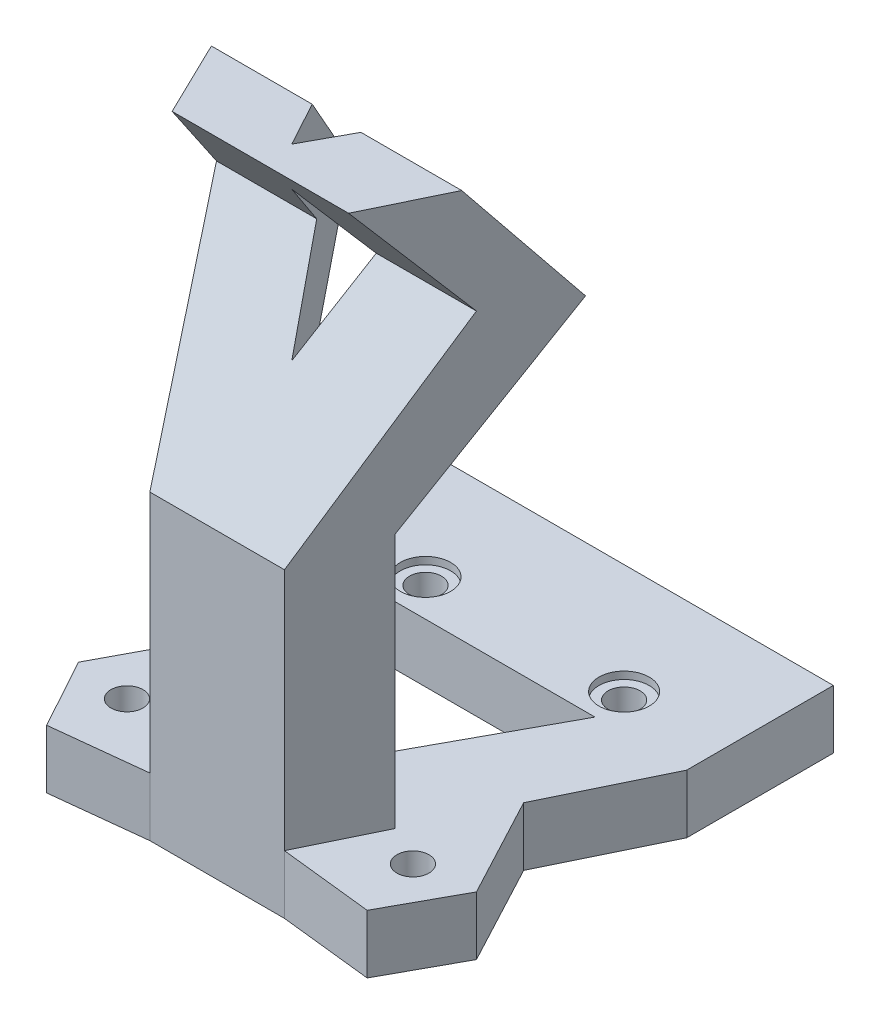
SolidWorks part; units mm, degrees
ref_plane "Front Plane" through (0, 0, 0) normal (0, 0, 1) x (1, 0, 0)
ref_plane "Top Plane" through (0, 0, 0) normal (0, 1, 0) x (1, 0, 0)
ref_plane "Right Plane" through (0, 0, 0) normal (1, 0, 0) x (0, 0, -1)
sketch "Sketch2" plane through (0, 0, 0) normal (0, 1, 0) x (1, 0, 0)
  line L0 (-47.1248, 0) -> (47.1248, 0) construction
  line L1 (-131.7903, 0) -> (131.7903, 0) construction
  line L2 (47.1248, 0) -> (-58.69, 0) construction
  line L3 (0, 0) -> (0, 70.6117) construction
  line L4 (0, 70.6117) -> (0, -77.9144) construction
  line L5 (-27.1, 0) -> (27.1, 0) construction
  line L6 (27.1, 0) -> (27.1, 20) construction
  line L7 (-27.1, 0) -> (27.1, 0)
  line L8 (27.1, 0) -> (27.1, 20)
  line L9 (27.1, 20) -> (-27.1, 20)
  line L10 (0, -131.4832) -> (0, 131.4832) construction
  line L11 (-27.1, 0) -> (-27.1, 20) construction
  line L12 (-47.1248, 0) -> (58.69, 0) construction
  line L13 (-27.1, 0) -> (-27.1, 20)
  point P4 (0, 0)
  point P8 (0, 0)
  point P19 (0, 20)
  dimension "D1" = 20
  dimension "D2" = 27.1
extrude "Boss-Extrude1" add sketch "Sketch2" along normal blind 8
ref_plane "Plane1" through (0, 5, 0) normal (0, 1, 0) x (1, 0, 0)
sketch "Sketch4" plane through (0, 8, 0) normal (0, 1, 0) x (1, 0, 0)
  line L0 (-27.1, 10) -> (-27.1, 0) construction
  line L1 (-4.4, 0) -> (4.4, 0) construction
  line L2 (-27.1, 20) -> (-27.1, 0) construction
  line L3 (-27.1, 0) -> (-27.1, 10) construction
  line L4 (-27.1, 10) -> (27.1, 10) construction
  line L5 (27.1, 0) -> (27.1, 20) construction
  line L6 (27.1, 10) -> (27.1, 0) construction
  line L8 (27.1, 0) -> (27.1, 5) construction
  line L9 (27.1, 5) -> (-27.1, 5) construction
  line L10 (0, 0) -> (27.1, 0) construction
  line L11 (-27.1, 0) -> (27.1, 0) construction
  line L12 (27.1, 0) -> (13.55, 0) construction
  line L13 (-13.55, 10) -> (-13.55, 0) construction
  line L14 (13.55, 0) -> (13.55, 10) construction
  line L15 (0, -4.4) -> (0, 4.4) construction
  circle A0 centre (13.55, 5) radius 2.1825
  circle A1 centre (-13.55, 5) radius 2.1825
  dimension "D1" = 4.365
extrude "Cut-Extrude1" cut sketch "Sketch4" against normal blind 10
sketch "Sketch5" plane through (0, 5, 0) normal (0, 1, 0) x (1, 0, 0)
  line L2 (-4.4, 0) -> (4.4, 0) construction
  line L4 (-27.1, 0) -> (-9.1823, -36.9742)
  line L6 (0, -24.7427) -> (0, 24.7427) construction
  line L7 (-9.1823, -36.9742) -> (9.1823, -36.9742)
  line L9 (27.1, 0) -> (9.1823, -36.9742)
  line L12 (-27.1, 0) -> (-14.58, 0)
  line L16 (-14.58, 0) -> (0, -26.7931)
  line L17 (14.58, 0) -> (0, -26.7931)
  line L18 (27.1, 0) -> (14.58, 0)
  line L19 (-27.1, 20) -> (-27.1, 0) construction
  point P17 (0, -36.9742)
  point P18 (0, 0)
  dimension "D3" = 18.3647
extrude "Boss-Extrude2" add sketch "Sketch5" along normal blind 3
sketch "Sketch9" plane through (0, 8, 0) normal (0, 1, 0) x (1, 0, 0)
  line L0 (0, 20) -> (0, -6.1) construction
  line L1 (27.1, 20) -> (-27.1, 20) construction
  line L2 (0, -27.3312) -> (0, 27.3312) construction
  line L3 (0, -6.1) -> (0, -26.7931) construction
  line L4 (0, -26.7931) -> (33.0841, -26.7931) construction
  line L5 (33.0841, -26.7931) -> (-31.5504, -26.7931) construction
  dimension "D1" = 26.1
sketch "Sketch10" plane through (0, 0, 0) normal (1, 0, 0) x (0, 0, -1)
  line L0 (-26.7931, 8) -> (-36.9742, 8) construction
  line L1 (-36.9742, 8) -> (-36.9742, 74.3965) construction
  line L2 (-26.7931, 8) -> (-26.7931, 70.9936) construction
  line L3 (-26.7931, 8) -> (-26.7931, 42.8)
  line L4 (-26.7931, 42.8) -> (-9.3053, 66.4334)
  line L5 (-9.3053, 66.4334) -> (-20.6818, 81.8078)
  line L6 (-20.6818, 81.8078) -> (-31.0856, 81.8078)
  line L7 (-31.0856, 81.8078) -> (-19.331, 67.2209)
  line L8 (-19.331, 67.2209) -> (-36.9742, 41.1983)
  line L9 (-36.9742, 41.1983) -> (-36.9742, 8)
  line L10 (-36.9742, 8) -> (-26.7931, 8)
  dimension "D1" = 34.8
  dimension "D2" = 216.5
  dimension "D3" = 29.4
  dimension "D4" = 107
  dimension "D5" = 107
extrude "Boss-Extrude4" add sketch "Sketch10" along normal mid plane 56
sketch "Sketch12" plane through (0, 0, 0) normal (0, 1, 0) x (1, 0, 0)
  line L1 (-14.58, 0) -> (14.58, 0)
  line L4 (-27.1, 0) -> (-9.1823, -36.9742)
  line L7 (-9.1823, -36.9742) -> (9.1823, -36.9742)
  line L9 (27.1, 0) -> (9.1823, -36.9742)
  line L16 (-14.58, 0) -> (0, -26.7931)
  line L17 (14.58, 0) -> (0, -26.7931)
  line L20 (-27.1, 0) -> (-49.7625, -38.9547)
  line L21 (-49.7625, -38.9547) -> (46.0387, -38.9547)
  line L22 (46.0387, -38.9547) -> (27.1, 0)
  point P17 (0, -36.9742)
  point P18 (0, 0)
  dimension "D3" = 18.3647
extrude "Cut-Extrude2" cut sketch "Sketch12" along normal blind 106
sketch "Sketch14" plane through (0, 0, 0) normal (0, 1, 0) x (1, 0, 0)
  line L4 (-27.1, 0) -> (-9.1823, -36.9742)
  line L7 (-9.1823, -36.9742) -> (9.1823, -36.9742)
  line L9 (27.1, 0) -> (9.1823, -36.9742)
  line L12 (-27.1, 0) -> (-14.58, 0)
  line L16 (-14.58, 0) -> (0, -26.7931)
  line L17 (14.58, 0) -> (0, -26.7931)
  line L18 (27.1, 0) -> (14.58, 0)
  point P17 (0, -36.9742)
  point P18 (0, 0)
  dimension "D3" = 18.3647
extrude "Boss-Extrude5" add sketch "Sketch14" along normal blind 5
sketch "Sketch15" plane through (0, 0, 0) normal (0, 1, 0) x (1, 0, 0)
  line L0 (19.8341, -14.9935) -> (27.1464, -28.7435)
  line L1 (27.1464, -28.7435) -> (21.8653, -38.3747)
  line L2 (21.8653, -38.3747) -> (9.1823, -36.9742)
  line L3 (9.1823, -36.9742) -> (19.8341, -14.9935)
  line L4 (0, -27.3312) -> (0, 27.3312) construction
  line L5 (-21.8653, -38.3747) -> (-9.1823, -36.9742)
  line L6 (-27.1464, -28.7435) -> (-21.8653, -38.3747)
  line L7 (-19.8341, -14.9935) -> (-27.1464, -28.7435)
  line L8 (-9.1823, -36.9742) -> (-19.8341, -14.9935)
  line L9 (22.5907, -9.3053) -> (17.0776, -20.6818) construction
extrude "Boss-Extrude6" add sketch "Sketch15" along normal blind 8
sketch "Sketch16" plane through (0, 8, 0) normal (0, 1, 0) x (1, 0, 0)
  line L0 (9.1823, -36.9742) -> (19.8341, -14.9935) construction
  line L1 (19.8341, -14.9935) -> (14.5082, -25.9838) construction
  line L2 (14.5082, -25.9838) -> (24.5059, -33.5591) construction
  line L3 (21.8653, -38.3747) -> (27.1464, -28.7435) construction
  line L4 (24.5059, -33.5591) -> (19.507, -29.7715) construction
  line L5 (0, -27.3312) -> (0, 27.3312) construction
  circle A0 centre (19.507, -29.7715) radius 2.1825
  circle A1 centre (-19.507, -29.7715) radius 2.1825
  dimension "D1" = 4.365
extrude "Cut-Extrude4" cut sketch "Sketch16" against normal blind 10
sketch "Sketch17" plane through (0, 8, 0) normal (0, 1, 0) x (1, 0, 0)
  line L0 (13.55, 5) -> (0, 5) construction
  line L1 (0, 20) -> (0, -6.1) construction
  line L2 (-13.55, 5) -> (0, 5) construction
  line L3 (0, -27.3312) -> (0, 27.3312) construction
  circle A0 centre (-13.55, 5) radius 3.4296
  circle A1 centre (13.55, 5) radius 3.4296
extrude "Cut-Extrude5" cut sketch "Sketch17" against normal blind 1
